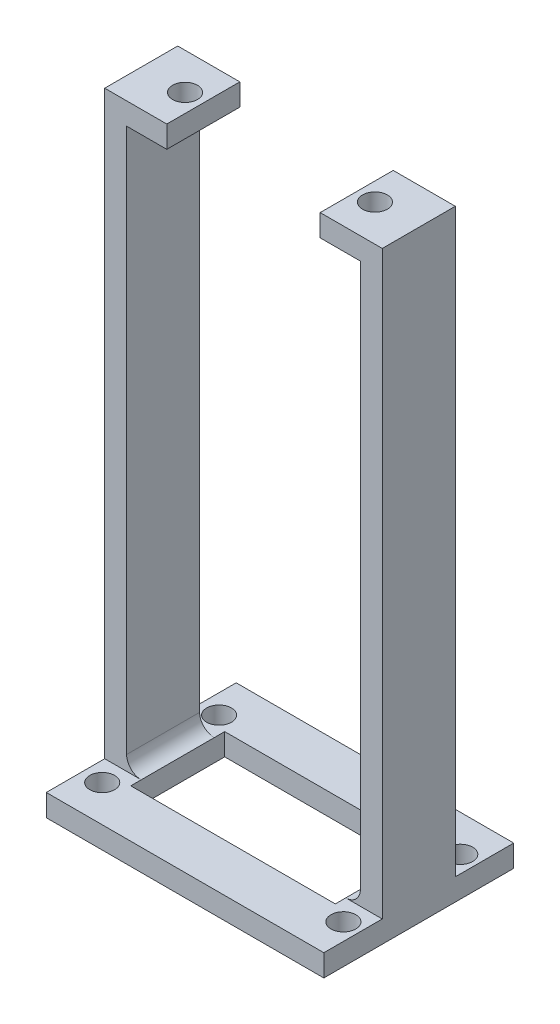
SolidWorks part; units mm, degrees
ref_plane "Front Plane" through (0, 0, 0) normal (0, 0, 1) x (1, 0, 0)
ref_plane "Top Plane" through (0, 0, 0) normal (0, 1, 0) x (1, 0, 0)
ref_plane "Right Plane" through (0, 0, 0) normal (1, 0, 0) x (0, 0, -1)
sketch "Sketch1" plane through (0, 0, 0) normal (0, 0, 1) x (1, 0, 0)
  line L0 (19, -3) -> (-19, -3)
  line L5 (19, 79.5) -> (10.5, 79.5)
  line L6 (-10.5, 79.5) -> (-10.5, 76.5)
  line L11 (16, 76.5) -> (10.5, 76.5)
  line L12 (-19, 79.5) -> (-19, 44.5833)
  line L14 (-19, 44.5833) -> (-19, -3)
  line L16 (-16, 76.5) -> (-16, 0)
  line L19 (-16, 0) -> (16, 0)
  line L21 (16, 0) -> (16, 76.5)
  line L22 (19, 79.5) -> (19, -3)
  line L23 (10.5, 79.5) -> (10.5, 76.5)
  line L24 (-10.5, 76.5) -> (-16, 76.5)
  line L25 (-10.5, 79.5) -> (-19, 79.5)
  point P14 (0, 0)
  dimension "D1" = 3
  dimension "D2" = 3
  dimension "D3" = 38
  dimension "D4" = 5.5
  dimension "D5" = 32
  dimension "D6" = 5.5
  dimension "D7" = 3
  dimension "D8" = 76.5
extrude "Boss-Extrude1" add sketch "Sketch1" along normal blind 5 and the other way blind 5
sketch "Sketch3" plane through (0, -3, 0) normal (0, -1, 0) x (-1, 0, 0)
  line L0 (19, 5) -> (19, -5) construction
  line L1 (19, -13) -> (-19, -13)
  line L2 (19, -13) -> (19, 13)
  line L3 (19, 13) -> (-19, 13)
  line L4 (-19, -13) -> (-19, 13)
  line L5 (19, -13) -> (-19, 13) construction
  line L6 (19, 13) -> (-19, -13) construction
  line L7 (19, 5) -> (-19, 5) construction
  point P0 (0, 0)
  dimension "D1" = 8
extrude "Boss-Extrude2" add sketch "Sketch3" against normal blind 3
sketch "Sketch4" plane through (0, -3, 0) normal (0, -1, 0) x (1, 0, 0)
  line L0 (19, 5) -> (19, 13) construction
  line L1 (14, 6.4306) -> (-14, 6.4306)
  line L2 (14, 6.4306) -> (14, -6.4306)
  line L3 (14, -6.4306) -> (-14, -6.4306)
  line L4 (-14, 6.4306) -> (-14, -6.4306)
  line L5 (14, 6.4306) -> (-14, -6.4306) construction
  line L6 (14, -6.4306) -> (-14, 6.4306) construction
  line L8 (-19, 13) -> (-19, 5) construction
  dimension "D1" = 5
  dimension "D2" = 5
hole_wizard "M3 Clearance Hole1" positions "Sketch6" profile "Sketch8" hole size "M3" standard "ISO" end condition up to next
sketch "Sketch6" plane through (0, 79.5, 0) normal (0, 1, 0) x (1, 0, 0)
  point P2 (-13, 0)
  point P5 (13, 0)
  point P9 (0, 0)
sketch "Sketch8" plane through (-13, 79.5, 0) normal (1, 0, 0) x (0, 0, 1)
  line L0 (0, 0) -> (0, 3)
  line L1 (0, 3) -> (1.7, 3)
  line L2 (1.7, 3) -> (1.7, 0)
  line L5 (1.7, 0) -> (0, 0)
  line L11 (0, -6.35) -> (0, 107.95) construction
  dimension "Thru Hole Dia." = 3.4
  dimension "Thru Hole Depth" = 3
sketch "Sketch9" plane through (0, 0, 0) normal (0, 1, 0) x (1, 0, 0)
  line L0 (19, 8) -> (-19, 8)
  line L3 (19, -8) -> (-19, -8)
  line L7 (-19, 13) -> (19, 13) construction
  line L8 (19, -13) -> (-19, -13) construction
  dimension "D1" = 5
  dimension "D2" = 5
fillet "Fillet3" radius 2 2 edges at (-16, 0, 0) (16, 0, 0)
hole_wizard "M3 Clearance Hole2" positions "Sketch12" profile "Sketch11" hole size "M3" standard "ISO"
sketch "Sketch12" plane through (0, 0, 0) normal (0, 1, 0) x (1, 0, 0)
  line L0 (19, -8) -> (-19, -8) construction
  line L1 (19, 8) -> (-19, 8) construction
  point P0 (16.68, -8)
  point P4 (-16.3409, -8)
  point P6 (16.68, 8)
  point P10 (-16.3409, 8)
sketch "Sketch11" plane through (16.68, 0, 8) normal (1, 0, 0) x (0, 0, 1)
  line L0 (0, 0) -> (0, 11.0215)
  line L1 (0, 11.0215) -> (1.7, 10)
  line L2 (1.7, 10) -> (1.7, 0)
  line L5 (1.7, 0) -> (0, 0)
  line L10 (0, 11.0215) -> (-1.7, 10) construction
  line L11 (0, -6.35) -> (0, 107.95) construction
  dimension "Hole Dia." = 3.4
  dimension "Hole Depth" = 10
  dimension "Drill Angle" = 118
extrude "Cut-Extrude2" cut sketch "Sketch4" against normal blind 3
